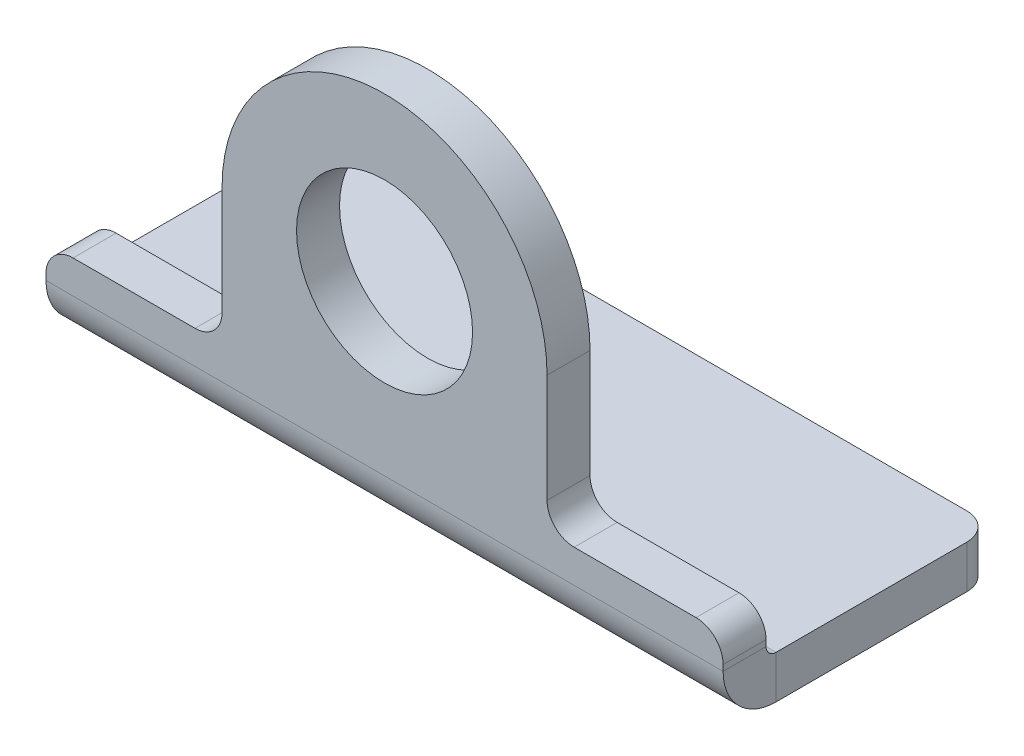
SolidWorks part; units mm, degrees
note: The reader was unsure of these and kept them because the rebuilt part matched: flange length of "Edge-Flange1".
ref_plane "Front Plane" through (0, 0, 0) normal (0, 0, 1) x (1, 0, 0)
ref_plane "Top Plane" through (0, 0, 0) normal (0, 1, 0) x (1, 0, 0)
ref_plane "Right Plane" through (0, 0, 0) normal (1, 0, 0) x (0, 0, -1)
sketch "Sketch1" plane through (0, 0, 0) normal (0, 0, 1) x (1, 0, 0)
  line L0 (-25, 0) -> (25, 0)
  line L1 (25, 0) -> (25, 1.175)
  line L2 (23, 3.175) -> (14, 3.175)
  line L3 (12, 5.175) -> (12, 13.175)
  line L4 (-12, 13.175) -> (-12, 5.175)
  line L5 (-14, 3.175) -> (-23, 3.175)
  line L6 (-25, 1.175) -> (-25, 0)
  arc A0 (12, 13.175) -> (-12, 13.175) centre (0, 13.175) ccw
  circle A1 centre (0, 13.175) radius 6.5
  arc A2 (25, 1.175) -> (23, 3.175) centre (23, 1.175) ccw
  arc A3 (-23, 3.175) -> (-25, 1.175) centre (-23, 1.175) ccw
  arc A4 (14, 3.175) -> (12, 5.175) centre (14, 5.175) cw
  arc A5 (-12, 5.175) -> (-14, 3.175) centre (-14, 5.175) cw
  point P3 (0, 0)
  point P4 (0, 0)
  point P13 (0, 0)
  point P16 (25, 3.175)
  point P21 (12, 3.175)
  dimension "D1" = 13
  dimension "D3" = 12
  dimension "D6" = 2
  dimension "D2" = 3.175
  dimension "D4" = 10
  dimension "D5" = 50
base flange "Base-Flange1" sketch "Sketch1" thickness 3.175 reverse thickness direction no parameters "D1"=0.7366
edge flange "Edge-Flange1" sketch "Sketch8" flange angle 90 flange length 20 flange position material outside bend radius 0.7366 thickness 3.175 relief rectangular parameters "D6"=10
sketch "Sketch8" plane through (0, 0, -3.175) normal (0, -1, 0) x (-1, 0, 0)
  line L0 (25, 0) -> (-25, 0) construction
  line L1 (25, 0) -> (-25, 0)
  line L2 (-25, 0) -> (-25, 16.825)
  line L3 (-25, 16.825) -> (25, 16.825)
  line L4 (25, 16.825) -> (25, 0)
bend "EdgeBend1" bend radius 0.7366 bend angle 90 parameters "D5"=1
fillet "Fillet2" radius 2 2 edges at (25, -1.5875, -20) (-25, -1.5875, -20)
sketch "Bend-Lines1" [suppressed] plane through (0, 0, 0) normal (0, 1, 0) x (1, 0, 0)
sketch "Bounding-Box1" [suppressed] plane through (0, 0, 0) normal (0, 1, 0) x (1, 0, 0)
sheet metal parameters "Sheet-Metal1" thickness 3.175 parameters "D1"=0.7366
flat pattern "Flat-Pattern1" [suppressed]
sketch "Bend-Lines2" plane through (0, 0, 0) normal (0, 1, 0) x (1, 0, 0)
sketch3d "Bounding-Box2" [suppressed]
  line L0 (25, 11.9999, 0) -> (-25, 11.9999, 0) construction
  line L1 (25, -19.175, 0) -> (-25, -19.175, 0) construction
  line L2 (25, 11.9999, 0) -> (25, -19.175, 0) construction
  line L3 (-25, 11.9999, 0) -> (-25, -19.175, 0) construction
sheet metal parameters "Sheet-Metal2" thickness 3.175 parameters "D1"=0.7366
flat pattern "Flat-Pattern1"
sketch "Bend-Lines2" plane through (0, 0, 0) normal (0, 0, 1) x (1, 0, 0)
  line L0 (-25, -1.0887) -> (25, -1.0887) construction
  line L1 (-25, -1.0887) -> (25, -1.0887) construction
sketch3d "Bounding-Box2" [suppressed]
  line L0 (-48, 23.9999, 0) -> (2, 23.9999, 0) construction
  line L1 (-48, -20.1775, 0) -> (2, -20.1775, 0) construction
  line L2 (-48, 23.9999, 0) -> (-48, -20.1775, 0) construction
  line L3 (2, 23.9999, 0) -> (2, -20.1775, 0) construction
bend of the flat pattern "Flatten-<EdgeBend1>1"
